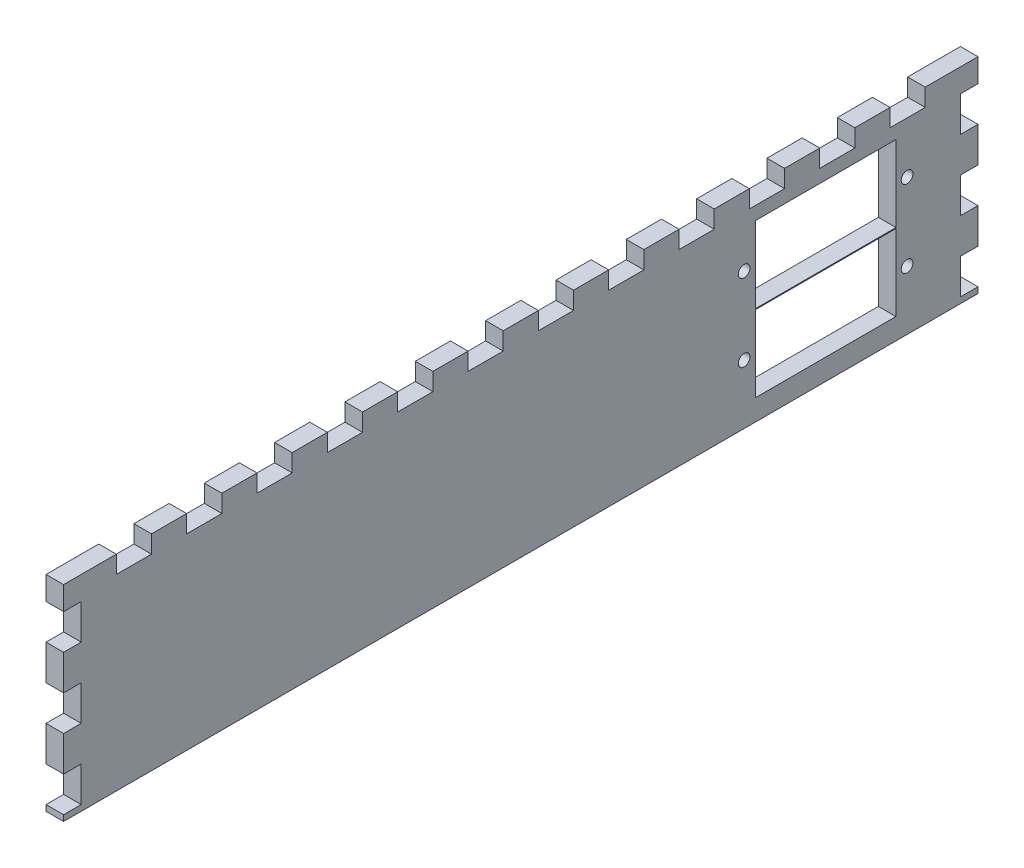
SolidWorks part; units mm, degrees
ref_plane "Front Plane" through (0, 0, 0) normal (0, 0, 1) x (1, 0, 0)
ref_plane "Top Plane" through (0, 0, 0) normal (0, 1, 0) x (1, 0, 0)
ref_plane "Right Plane" through (0, 0, 0) normal (1, 0, 0) x (0, 0, -1)
sketch "Sketch1" plane through (0, 0, 0) normal (1, 0, 0) x (0, 0, -1)
  line L1 (-75, 16) -> (75, 16)
  line L2 (-75, 16) -> (-75, -16)
  line L3 (-75, -16) -> (75, -16)
  line L4 (75, 16) -> (75, -16)
  line L5 (-75, 16) -> (75, -16) construction
  line L6 (-75, -16) -> (75, 16) construction
  point P0 (0, 0)
  dimension "D1" = 150
  dimension "D2" = 32
extrude "Boss-Extrude1" add sketch "Sketch1" along normal blind 3
sketch "Sketch3" plane through (0, 0, -75) normal (0, 0, -1) x (-1, 0, 0)
  line L0 (0, 0) -> (-3, 0) construction
  line L1 (0, -16) -> (0, 16) construction
  line L2 (-3, -16) -> (-3, 16) construction
  line L4 (0, 3) -> (-3, 3)
  line L5 (0, 3) -> (0, 9)
  line L6 (0, 9) -> (-3, 9)
  line L7 (-3, 3) -> (-3, 9)
  line L8 (0, 3) -> (-3, 9) construction
  line L9 (0, 9) -> (-3, 3) construction
  point P10 (-1.5, 6)
  dimension "D1" = 3
  dimension "D2" = 6
extrude "Boss-Extrude2" add sketch "Sketch3" along normal blind 3
pattern_linear "LPattern1" count 3 spacing 12 along (0, -1, 0) count 2 spacing 12 along (0, 1, 0) of "Boss-Extrude2" pattern seed only yes
ref_plane "Plane1" through (0, -16, 0) normal (0, -1, 0) x (-1, 0, 0)
sketch "Sketch4" plane through (0, 16, 0) normal (0, 1, 0) x (1, 0, 0)
  line L0 (0, 0) -> (3, 0) construction
  line L1 (0, 75) -> (0, -75) construction
  line L2 (3, 75) -> (3, -75) construction
  line L4 (0, -3) -> (3, -3)
  line L5 (0, -3) -> (0, 3)
  line L6 (0, 3) -> (3, 3)
  line L7 (3, -3) -> (3, 3)
  line L8 (0, -3) -> (3, 3) construction
  line L9 (0, 3) -> (3, -3) construction
  point P7 (1.5, 0)
  dimension "D1" = 6
extrude "Boss-Extrude3" add sketch "Sketch4" along normal blind 3
pattern_linear "LPattern2" count 7 spacing 12 along (0, 0, -1) count 7 spacing 12 along (0, 0, 1) of "Boss-Extrude3" pattern seed only yes
ref_plane "Plane2" through (0, 0, 0) normal (0, 0, 1) x (1, 0, 0)
sketch "Sketch5" plane through (0, 0, 0) normal (-1, 0, 0) x (0, 0, 1)
  line L0 (-78, -21) -> (-78, -15) construction
  line L1 (-75, 19) -> (-78, 19)
  line L2 (-75, 19) -> (-75, 21)
  line L3 (-75, 21) -> (-78, 21)
  line L4 (-78, 19) -> (-78, 21)
  line L5 (-75, 19) -> (-78, 21) construction
  line L6 (-75, 21) -> (-78, 19) construction
  line L7 (-75, -21) -> (-78, -21)
  line L8 (-75, -21) -> (-75, -16)
  line L9 (-75, -16) -> (-78, -16)
  line L10 (-78, -21) -> (-78, -16)
  line L11 (-75, -21) -> (-78, -16) construction
  line L12 (-75, -16) -> (-78, -21) construction
  line L13 (75, -16) -> (-75, -16) construction
  point P4 (-76.5, 20)
  point P11 (-76.5, -18.5)
extrude "Cut-Extrude1" cut sketch "Sketch5" against normal blind 3
mirror "Mirror1" about plane through (0, 0, 0) normal (0, 0, 1) of "LPattern1"
mirror "Mirror2" about plane through (0, 0, 0) normal (0, 0, 1) of "Cut-Extrude1"
sketch "Sketch6" plane through (3, 0, 0) normal (1, 0, 0) x (0, 0, -1)
  line L0 (52, 0.6017) -> (52, -12.3983) construction
  line L1 (40, 0.6017) -> (64, 0.6017)
  line L2 (40, 0.6017) -> (40, -12.3983)
  line L3 (40, -12.3983) -> (64, -12.3983)
  line L4 (64, 0.6017) -> (64, -12.3983)
  line L5 (40, 0.6017) -> (64, -12.3983) construction
  line L6 (40, -12.3983) -> (64, 0.6017) construction
  line L7 (52, 13.7579) -> (52, 0.7579) construction
  line L8 (40, 13.7579) -> (64, 13.7579)
  line L9 (40, 13.7579) -> (40, 0.7579)
  line L10 (40, 0.7579) -> (64, 0.7579)
  line L11 (64, 13.7579) -> (64, 0.7579)
  line L12 (40, 13.7579) -> (64, 0.7579) construction
  line L13 (40, 0.7579) -> (64, 13.7579) construction
  line L14 (-75, -9) -> (-75, -15) construction
  circle A0 centre (38.1, -5.8983) radius 1
  circle A1 centre (65.9, -5.8983) radius 1
  circle A2 centre (38.1, 7.2579) radius 1
  circle A3 centre (65.9, 7.2579) radius 1
  point P9 (52, -5.8983)
  point P11 (52, -5.8983)
  point P21 (52, 7.2579)
  point P23 (52, 7.2579)
  point P24 (44.7125, -5.8983)
  dimension "D1" = 2
  dimension "D5" = 2
  dimension "D2" = 27.8
  dimension "D3" = 24
  dimension "D4" = 13
  dimension "D6" = 27.8
  dimension "D7" = 24
  dimension "D8" = 13
  dimension "D9" = 115
extrude "Cut-Extrude2" cut sketch "Sketch6" against normal through all
